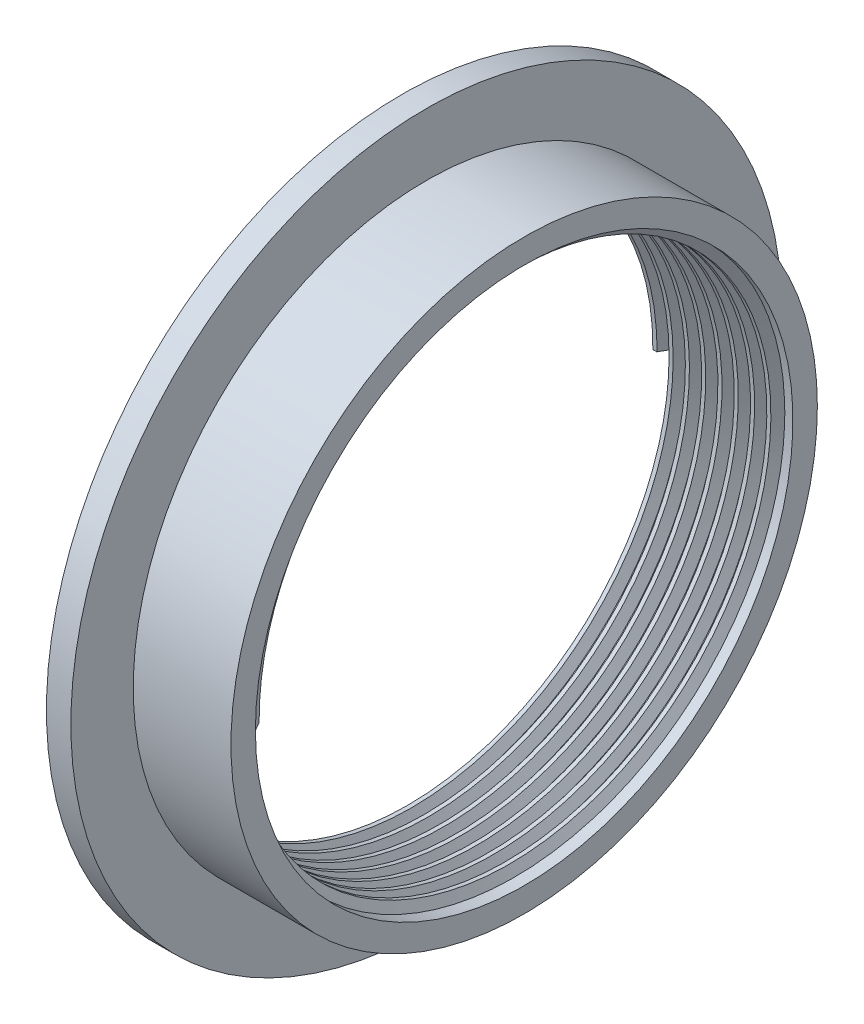
SolidWorks part; units mm, degrees
ref_plane "Front Plane" through (0, 0, 0) normal (0, 0, 1) x (1, 0, 0)
ref_plane "Top Plane" through (0, 0, 0) normal (0, 1, 0) x (1, 0, 0)
ref_plane "Right Plane" through (0, 0, 0) normal (1, 0, 0) x (0, 0, -1)
sketch "Sketch1" plane through (0, 0, 0) normal (1, 0, 0) x (0, 0, -1)
  circle A1 centre (0, 0) radius 26.2765 construction
  circle A3 centre (0, 0) radius 23.1015
  circle A4 centre (0, 0) radius 17.4625
  dimension "D1" = 34.925
  dimension "D2" = 52.553
  dimension "D3" = 3.175
extrude "Boss-Extrude1" add sketch "Sketch1" along normal mid plane 1.5875 contours A3 A4 region at (0, 0, 22.4481)
sketch "Sketch2" plane through (0.7937, 0, 0) normal (1, 0, 0) x (0, 0, -1)
  circle A0 centre (0, 0) radius 19.05
  circle A1 centre (0, 0) radius 17.4625
  dimension "D1" = 38.1
extrude "Boss-Extrude2" add sketch "Sketch2" along normal blind 6.35 contours A0 A1 region at (0.7937, 0, 18.5112)
thread "Thread1" pitch 1.0583 method extrude profile "Thread Profile1" start angle 0, offset 0, length 0, pitch 1.0583, diameter 34.925
ref_plane "Plane1" through (7.1437, 0, 17.4625) normal (0, -1, 0) x (0, 0, 1)
sketch "Thread Profile1" plane through (7.1437, 0, 17.4625) normal (0, -1, 0) x (0, 0, 1)
  line L0 (0, 0) -> (0, 1.0583) construction
  line L11 (0, 0) -> (0, 0.926)
  line L12 (0, 0.926) -> (-0.5728, 0.5953)
  line L13 (-0.5728, 0.5953) -> (-0.5728, 0.3307)
  line L15 (-0.5728, 0.3307) -> (0, 0)
  line L17 (-0.5728, 0.463) -> (0, 0.463) construction
  point P2 (0, 0)
  dimension "Pitch" = 1.0583
  dimension "Profile_Angle" = 60
  dimension "Profile_Land" = 0.2646
  dimension "Profile_Height" = 0.5728
